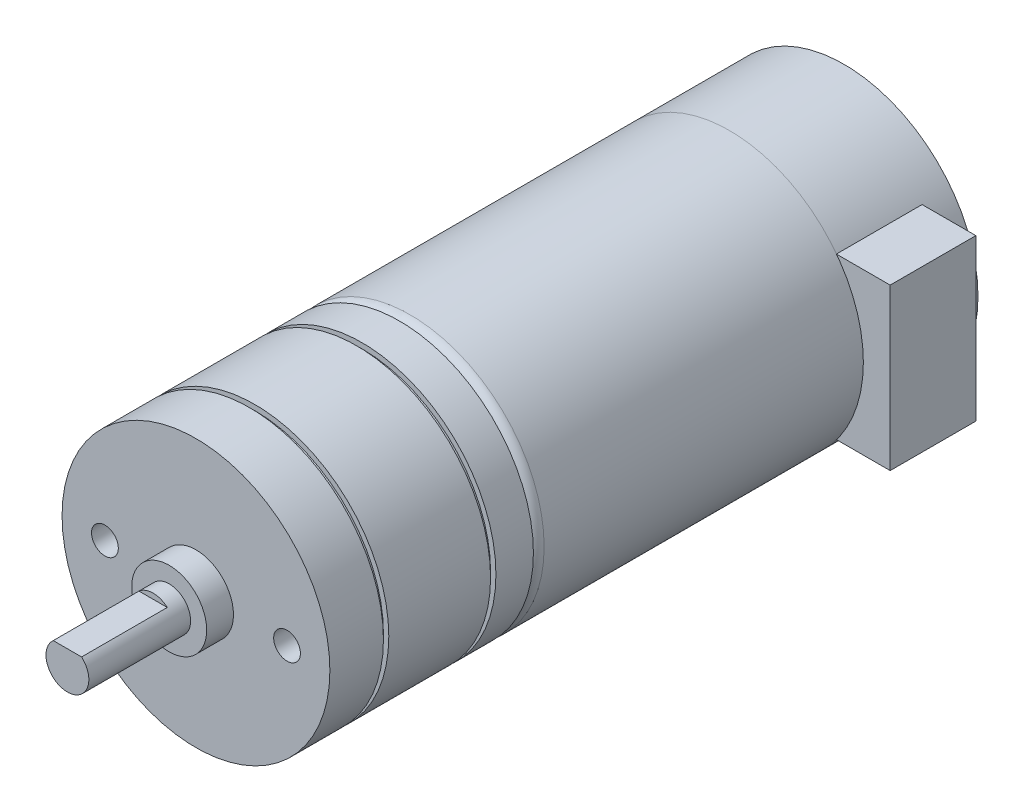
SolidWorks part; units mm, degrees
material "5052-O"
ref_plane "前基準面" through (0, 0, 0) normal (0, 0, 1) x (1, 0, 0)
ref_plane "上基準面" through (0, 0, 0) normal (0, 1, 0) x (1, 0, 0)
ref_plane "右基準面" through (0, 0, 0) normal (1, 0, 0) x (0, 0, -1)
sketch "草圖1" plane through (0, 0, 0) normal (0, 0, 1) x (1, 0, 0)
  circle A0 centre (0, 0) radius 12.5
  dimension "D1" = 25
extrude "填料-伸長1" add sketch "草圖1" along normal blind 30.8
sketch "草圖2" plane through (0, 0, 0) normal (0, 0, -1) x (-1, 0, 0)
  circle A1 centre (0, 0) radius 12.5
  circle A2 centre (0, 0) radius 12.5
  dimension "D1" = 0
extrude "填料-伸長2" add sketch "草圖2" along normal blind 10.7 separate body
sketch "草圖3" plane through (0, 0, 0) normal (1, 0, 0) x (0, 0, -1)
  line L0 (0, -12.5) -> (0, 12.5) construction
  line L1 (0, -7.5) -> (8, -7.5)
  line L2 (0, -7.5) -> (0, 7.5)
  line L3 (0, 7.5) -> (8, 7.5)
  line L4 (8, -7.5) -> (8, 7.5)
  dimension "D1" = 15
  dimension "D2" = 8
extrude "填料-伸長3" add sketch "草圖3" along normal blind 15 separate body
fillet "圓角1" radius 1 1 edges at (12.5, 0, 30.8)
sketch "草圖4" plane through (0, 0, 30.8) normal (0, 0, 1) x (1, 0, 0)
  circle A0 centre (0, 0) radius 12.5
  dimension "D1" = 25
extrude "填料-伸長4" add sketch "草圖4" along normal blind 19 separate body
sketch "草圖5" plane through (0, 0, 49.8) normal (0, 0, 1) x (1, 0, 0)
  circle A0 centre (0, 0) radius 12.5
  circle A1 centre (0, 0) radius 12
  dimension "D1" = 24
  dimension "D2" = 25
extrude "除料-伸長1" cut sketch "草圖5" against normal blind 0.5 from offset 15 offset against normal yes
pattern_linear "直線複製排列1" count 2 spacing 10 along (0, 0, 1) of "除料-伸長1"
sketch "草圖6" plane through (0, 0, 49.8) normal (0, 0, 1) x (1, 0, 0)
  circle A0 centre (0, 0) radius 3.5
  dimension "D1" = 7
extrude "填料-伸長5" add sketch "草圖6" along normal blind 2.5 separate body
sketch "草圖7" plane through (0, 0, 52.3) normal (0, 0, 1) x (1, 0, 0)
  circle A0 centre (0, 0) radius 2
  dimension "D1" = 4
extrude "填料-伸長6" add sketch "草圖7" along normal blind 9.5
sketch "草圖8" plane through (0, 0, 61.8) normal (0, 0, 1) x (1, 0, 0)
  line L0 (-1.3229, 1.5) -> (1.3229, 1.5)
  circle A0 centre (0, 0) radius 2 construction
  arc A1 (-1.3229, 1.5) -> (1.3229, 1.5) centre (0, 0) cw
  circle M2 centre (0, 0) radius 2
  dimension "D1" = 1.5
extrude "除料-伸長2" cut sketch "草圖8" against normal blind 8 contours L0 M2 region at (0, 1.7023, 61.8)
hole_wizard "M3x0.5 螺紋孔1" positions "草圖10" profile "草圖12" tap size "M3x0.5" standard "Ansi Metric"
sketch "草圖10" plane through (0, 0, 49.8) normal (0, 0, 1) x (1, 0, 0)
  circle A0 centre (0, 0) radius 8.5 construction
  point P3 (-8.5, 0)
  point P5 (8.5, 0)
  dimension "D1" = 17
sketch "草圖12" plane through (8.5, 0, 49.8) normal (1, 0, 0) x (0, -1, 0)
  line L0 (0, 0) -> (0, 5.7511)
  line L1 (0, 5.7511) -> (1.25, 5)
  line L2 (1.25, 5) -> (1.25, 0)
  line L5 (1.25, 0) -> (0, 0)
  line L10 (0, 5.7511) -> (-1.25, 5) construction
  line L11 (0, -6.35) -> (0, 107.95) construction
  dimension "螺孔鑽直徑" = 2.5
  dimension "螺孔鑽深度" = 5
  dimension "導頭角度" = 118
